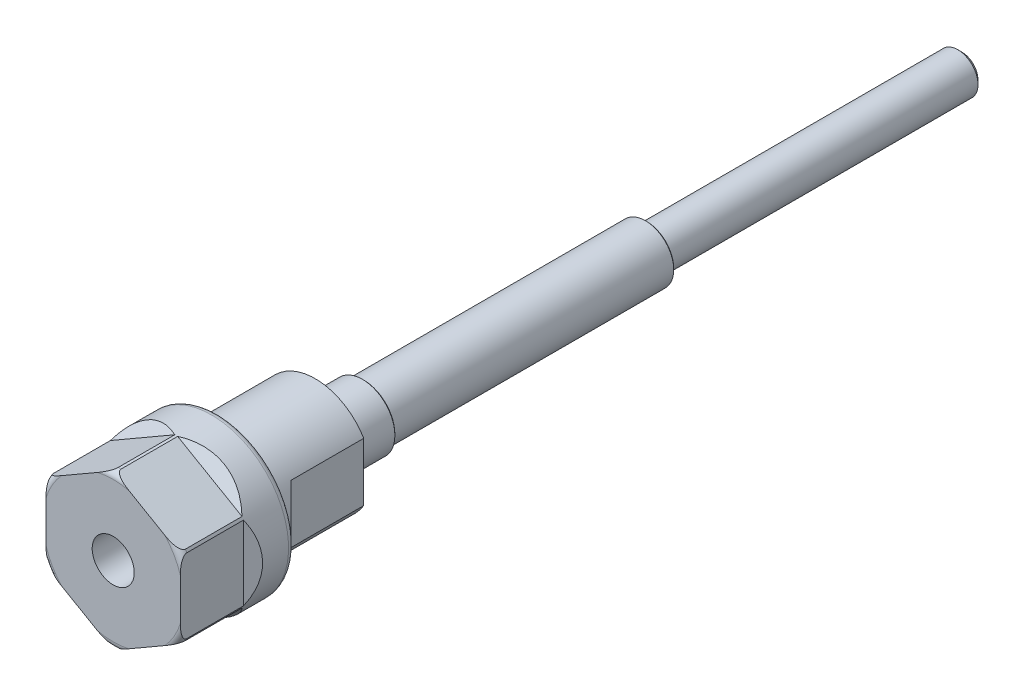
SolidWorks part; units mm, degrees
material "1023 Carbon Steel Sheet (SS)"
ref_plane "Plan de face" through (0, 0, 0) normal (0, 0, 1) x (1, 0, 0)
ref_plane "Plan de dessus" through (0, 0, 0) normal (0, 1, 0) x (1, 0, 0)
ref_plane "Plan de droite" through (0, 0, 0) normal (1, 0, 0) x (0, 0, -1)
sketch "Esquisse1" plane through (0, 0, 0) normal (0, 0, 1) x (1, 0, 0)
  circle A0 centre (0, 0) radius 4
  dimension "D1" = 8
extrude "Boss.-Extru.1" add sketch "Esquisse1" along normal blind 80
sketch "Sketch5" plane through (0, 0, 0) normal (0, 0, -1) x (-1, 0, 0)
  circle A0 centre (0, 0) radius 2.5
extrude "Cut-Extrude6" cut sketch "Sketch5" against normal blind 39 flip side to cut
chamfer "Chamfer4" distance 0.5 angle 45 2 edges at (-2.5, 0, 0) (-4, 0, 39)
sketch "Sketch6" plane through (0, 0, 0) normal (0, 0, -1) x (-1, 0, 0)
  circle A0 centre (0, 0) radius 3.5
extrude "Cut-Extrude7" cut sketch "Sketch6" against normal offset from surface (74 mm away) 6 flip side to cut up to face at (4, 0, 80)
chamfer "Chamfer5" distance 0.15 angle 45 2 edges at (4, 0, 74) (3.5, 0, 39)
sketch "Esquisse2" plane through (0, 0, 80) normal (0, 0, 1) x (1, 0, 0)
  circle A0 centre (0, 0) radius 9.5
  dimension "D1" = 19
extrude "Boss.-Extru.2" add sketch "Esquisse2" along normal blind 25
chamfer "Chanfrein1" distance 1 angle 45 1 edges at (9.5, 0, 80)
sketch "Sketch1" plane through (0, 0, 80) normal (0, 0, -1) x (-1, 0, 0)
  circle A0 centre (0, 0) radius 7
  dimension "D1" = 14
extrude "Cut-Extrude1" cut sketch "Sketch1" against normal blind 12 flip side to cut
sketch "Sketch2" plane through (0, 0, 80) normal (0, 0, -1) x (-1, 0, 0)
  line L1 (-6, -9.9735) -> (6, -9.9735)
  line L2 (-6, -9.9735) -> (-6, 9.9735)
  line L3 (-6, 9.9735) -> (6, 9.9735)
  line L4 (6, -9.9735) -> (6, 9.9735)
  line L5 (-6, -9.9735) -> (6, 9.9735) construction
  line L6 (-6, 9.9735) -> (6, -9.9735) construction
  point P0 (0, 0)
  dimension "D1" = 12
extrude "Cut-Extrude3" cut sketch "Sketch2" against normal blind 10 flip side to cut
chamfer "Chamfer1" distance 1 angle 45 2 edges at (-6, 0, 90) (6, 0, 90)
fillet "Fillet1" radius 0.8 2 edges at (9.5, 0, 105) (-9.5, 0, 92)
sketch "Sketch3" plane through (0, 0, 105) normal (0, 0, 1) x (1, 0, 0)
  circle A0 centre (0, 0) radius 2.6
  dimension "D1" = 5.2
extrude "Cut-Extrude4" cut sketch "Sketch3" against normal blind 12
sketch "Sketch4" plane through (0, 0, 105) normal (0, 0, 1) x (1, 0, 0)
  line L1 (0, 9.6) -> (-8.3138, 4.8)
  line L2 (-8.3138, 4.8) -> (-8.3138, -4.8)
  line L3 (-8.3138, -4.8) -> (0, -9.6)
  line L4 (0, -9.6) -> (8.3138, -4.8)
  line L5 (8.3138, -4.8) -> (8.3138, 4.8)
  line L6 (8.3138, 4.8) -> (0, 9.6)
  circle A0 centre (0, 0) radius 8.3138 construction
  dimension "D1" = 9.6
extrude "Cut-Extrude5" cut sketch "Sketch4" against normal blind 9 flip side to cut
chamfer "Chamfer2" distance 1.2 angle 45 6 edges at (4.1569, 7.2, 96) (8.3138, 0, 96) (4.1569, -7.2, 96) (-4.1569, -7.2, 96) (-8.3138, 0, 96) (-4.1569, 7.2, 96)
